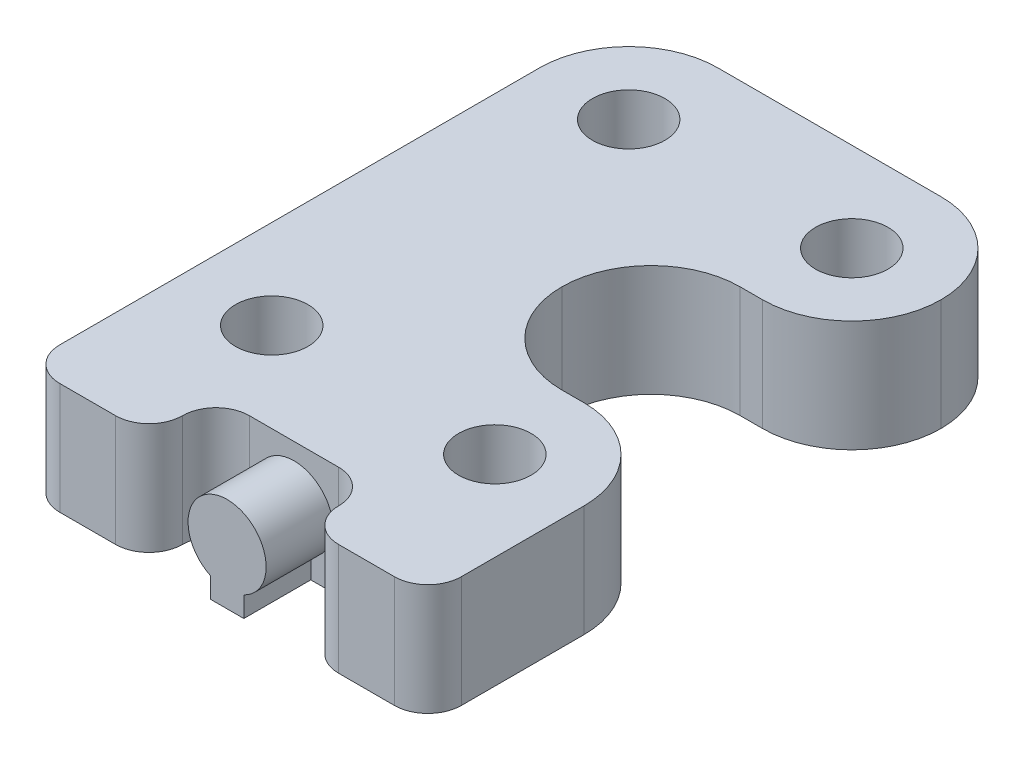
SolidWorks part; units mm, degrees
ref_plane "Front Plane" through (0, 0, 0) normal (0, 0, 1) x (1, 0, 0)
ref_plane "Top Plane" through (0, 0, 0) normal (0, 1, 0) x (1, 0, 0)
ref_plane "Right Plane" through (0, 0, 0) normal (1, 0, 0) x (0, 0, -1)
sketch "Sketch1" plane through (0, 0, 0) normal (0, 1, 0) x (1, 0, 0)
  line L0 (4, 27) -> (4, 5.375) construction
  line L1 (0, 0) -> (5.5, 0)
  line L2 (0, 0) -> (0, 27)
  line L3 (0, 27) -> (18, 27)
  line L4 (18, 0) -> (18, 11)
  line L5 (14, 27) -> (14, 5.375) construction
  line L6 (18, 19) -> (18, 27)
  line L7 (18, 19) -> (9, 19)
  line L8 (12.5, 0) -> (18, 0)
  line L9 (18, 11) -> (9, 11)
  line L10 (9, 19) -> (9, 11)
  line L11 (5.5, 3) -> (5.5, 0) construction
  line L12 (5.5, 0) -> (5.5, 3)
  line L13 (5.5, 3) -> (12.5, 3)
  line L14 (12.5, 0) -> (12.5, 3)
  line L15 (12.5, 3) -> (12.5, 0) construction
  circle A0 centre (4, 23) radius 1.625
  circle A1 centre (14, 23) radius 1.625
  circle A2 centre (14, 7) radius 1.625
  circle A3 centre (4, 7) radius 1.625
  dimension "D5" = 3.25
  dimension "D6" = 3.25
  dimension "D7" = 3.25
  dimension "D8" = 3.25
  dimension "D1" = 18
  dimension "D2" = 27
  dimension "D3" = 4
  dimension "D4" = 4
  dimension "D9" = 4
  dimension "D10" = 7
  dimension "D11" = 9
  dimension "D12" = 8
  dimension "D13" = 11
  dimension "D14" = 3
  dimension "D15" = 5.5
  dimension "D16" = 5.5
extrude "Boss-Extrude1" add sketch "Sketch1" along normal blind 5
fillet "Fillet1" radius 4 6 edges at (9, 2.5, -11) (9, 2.5, -19) (18, 2.5, -11) (0, 2.5, -27) (18, 2.5, -27) (18, 2.5, -19)
fillet "Fillet3" radius 1.5 6 edges at (12.5, 2.5, -3) (18, 2.5, 0) (12.5, 2.5, 0) (5.5, 2.5, -3) (5.5, 2.5, 0) (0, 2.5, 0)
sketch "Sketch3" plane through (0, 0, -3) normal (0, 0, 1) x (1, 0, 0)
  line L0 (11, 0) -> (11, 5) construction
  line L1 (7, 5) -> (7, 0) construction
  line L2 (7, 0) -> (11, 0) construction
  line L4 (8.25, 0.9189) -> (8.25, 0)
  line L5 (8.25, 0) -> (9.75, 0)
  line L6 (9.75, 0.9189) -> (9.75, 0)
  arc A0 (9.75, 0.9189) -> (8.25, 0.9189) centre (9, 2.5) ccw
  point P4 (9, 0)
  dimension "D3" = 3.5
  dimension "D1" = 2
  dimension "D2" = 2.5
  dimension "D4" = 1.25
  dimension "D5" = 1.25
extrude "Boss-Extrude2" add sketch "Sketch3" along normal up to surface (3 mm away) up to face at (2.75, 2.5, 0)
